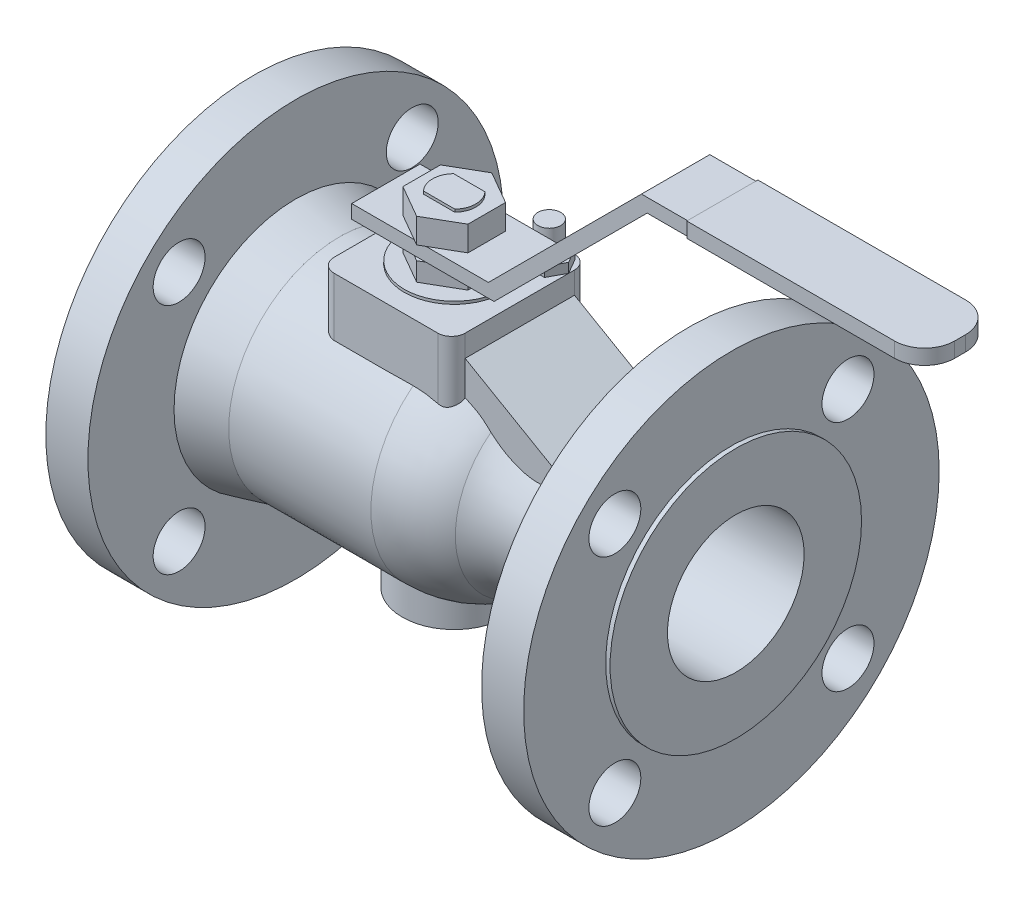
SolidWorks part; units mm, degrees
ref_plane "Alzado" through (0, 0, 0) normal (0, 0, 1) x (1, 0, 0)
ref_plane "Planta" through (0, 0, 0) normal (0, 1, 0) x (1, 0, 0)
ref_plane "Vista lateral" through (0, 0, 0) normal (1, 0, 0) x (0, 0, -1)
sketch "Sketch1" plane through (0, 0, 0) normal (0, 1, 0) x (1, 0, 0)
  line L0 (0, 0) -> (-58, 0)
  line L2 (0, 0) -> (86, 0)
  line L82 (86, -25) -> (86, 0)
  line L83 (103, -25) -> (86, -25)
  line L84 (103, -46) -> (103, -25)
  line L85 (101.4, -46) -> (103, -46)
  line L86 (101.4, -76) -> (101.4, -46)
  line L87 (86, -76) -> (101.4, -76)
  line L88 (86, -46.5259) -> (86, -76)
  line L89 (60.6645, -29.1709) -> (77.9489, -35.1943)
  line L90 (-42, -40.5) -> (10, -40.5)
  line L91 (-58, -44.5) -> (-42, -40.5)
  line L92 (-58, -76) -> (-58, -44.5)
  line L93 (-73.4, -76) -> (-58, -76)
  line L94 (-73.4, -46) -> (-73.4, -76)
  line L95 (-75, -46) -> (-73.4, -46)
  line L96 (-75, -25) -> (-75, -46)
  line L97 (-58, -25) -> (-75, -25)
  line L98 (-58, 0) -> (-58, -25)
  arc A10 (86, -46.5259) -> (77.9489, -35.1943) centre (74, -46.5259) ccw
  arc A11 (60.6645, -29.1709) -> (33.4338, -33.0319) centre (50.7922, -57.5) ccw
  spline S5 degree 3 poles (10, -40.5) (10.5262, -40.5101) (11.0548, -40.5089) (12.1058, -40.4845) (12.6294, -40.4614) (14.1952, -40.3616) (15.2323, -40.2548) (18.3249, -39.8235) (20.3622, -39.3913) (23.3756, -38.4904) (24.3775, -38.1449) (26.3277, -37.3691) (27.2787, -36.9384) (30.0543, -35.5088) (31.8008, -34.3712) (33.4338, -33.0319) knots 0 0 0 0 0.0625 0.0625 0.125 0.125 0.25 0.25 0.5 0.5 0.625 0.625 0.75 0.75 1 1 1 1
revolve "Revolve1" add sketch "Sketch1" angle 360 about L0
sketch "Sketch2" plane through (0, 0, 0) normal (1, 0, 0) x (0, 0, -1)
  circle A4 centre (-42.6385, 42.6385) radius 9.5
  circle A5 centre (-42.6385, -42.6385) radius 9.5
  circle A6 centre (42.6385, 42.6385) radius 9.5
  circle A7 centre (42.6385, -42.6385) radius 9.5
extrude "Cut-Extrude1" cut sketch "Sketch2" against normal through all both and the other way through all
sketch "Sketch3" plane through (0, 0, 0) normal (0, 1, 0) x (1, 0, 0)
  circle A2 centre (0, 0) radius 19
extrude "Boss-Extrude1" add sketch "Sketch3" against normal blind 49.5 separate body
sketch "Sketch4" plane through (0, 0, 0) normal (0, 1, 0) x (1, 0, 0)
  line L27 (19, 25) -> (-19, 25)
  line L28 (-24, 20) -> (-24, -20)
  line L29 (-19, -25) -> (19, -25)
  line L30 (24, -20) -> (24, 20)
  arc A8 (24, 20) -> (19, 25) centre (19, 20) ccw
  arc A9 (-19, 25) -> (-24, 20) centre (-19, 20) ccw
  arc A10 (-24, -20) -> (-19, -25) centre (-19, -20) ccw
  arc A11 (19, -25) -> (24, -20) centre (19, -20) ccw
extrude "Boss-Extrude2" add sketch "Sketch4" along normal blind 53 separate body
sketch "Sketch5" plane through (0, 53, 0) normal (0, 1, 0) x (1, 0, 0)
  line L22 (20.882, 12.1277) -> (14.4734, 12.1277)
  line L23 (14.4734, 12.1277) -> (11.2691, 17.6777)
  line L24 (11.2691, 17.6777) -> (14.4734, 23.2277)
  line L25 (14.4734, 23.2277) -> (20.882, 23.2277)
  line L26 (20.882, 23.2277) -> (24, 17.8271)
  line L32 (24, 17.8271) -> (20.882, 12.1277)
extrude "Boss-Extrude3" add sketch "Sketch5" along normal blind 3.5 separate body
sketch "Sketch6" plane through (0, 56.5, 0) normal (0, 1, 0) x (1, 0, 0)
  circle A0 centre (17.2247, 17.5586) radius 4.1811
extrude "Boss-Extrude4" add sketch "Sketch6" along normal blind 10.5 separate body
sketch "Sketch7" plane through (0, 0, 0) normal (0, 0, 1) x (1, 0, 0)
  line L0 (0, 0) -> (131.7104, 0) construction
  line L4 (63.1369, 22.4043) -> (24, 45)
  line L5 (24, 45) -> (24.0001, 32.3146)
  spline S6 degree 3 poles (33.4338, 26.2889) (34.3576, 25.4654) (35.3154, 24.6958) (37.3021, 23.2697) (38.331, 22.6131) (40.4691, 21.4275) (41.5792, 20.8979) (43.893, 19.9956) (45.0677, 19.6346) (47.4558, 19.1103) (48.6693, 18.947) (50.522, 18.8671) (51.1466, 18.8683) (52.3887, 18.9271) (53.0096, 18.9848) (54.8557, 19.2385) (56.0549, 19.513) (58.3989, 20.2432) (59.5438, 20.6989) (60.6645, 21.2354) knots 0 0 0 0 0.125 0.125 0.25 0.25 0.375 0.375 0.5 0.5 0.625 0.625 0.6875 0.6875 0.75 0.75 0.875 0.875 1 1 1 1
  spline S7 degree 3 poles (60.6645, 21.2354) (61.4867, 21.629) (62.311, 22.0185) (63.1369, 22.4043) knots 0 0 0 0 1 1 1 1
  spline S8 degree 3 poles (24.0001, 32.3146) (24.8648, 31.9406) (25.7146, 31.5304) (27.3704, 30.6494) (28.1774, 30.1777) (29.7503, 29.1727) (30.516, 28.6394) (32.0063, 27.511) (32.7311, 26.9166) (33.4338, 26.2889) knots 0 0 0 0 0.25 0.25 0.5 0.5 0.75 0.75 1 1 1 1
extrude "Boss-Extrude5" add sketch "Sketch7" along normal blind 20 and the other way blind 20 separate body
sketch "Sketch8" plane through (0, 53, 0) normal (0, 1, 0) x (1, 0, 0)
  line L0 (0, 0) -> (29.0528, -1.511) construction
  circle A1 centre (0, 0) radius 18.25
extrude "Boss-Extrude6" add sketch "Sketch8" along normal blind 1 separate body
sketch "Sketch9" plane through (0, 54, 0) normal (0, 1, 0) x (1, 0, 0)
  line L0 (0, 0) -> (32.4906, 0) construction
  line L13 (-11.9, 6.8705) -> (-11.9, -6.8705)
  line L14 (-11.9, -6.8705) -> (0, -13.7409)
  line L15 (0, -13.7409) -> (11.9, -6.8705)
  line L16 (11.9, -6.8705) -> (11.9, 6.8705)
  line L17 (11.9, 6.8705) -> (0, 13.7409)
  line L18 (0, 13.7409) -> (-11.9, 6.8705)
extrude "Boss-Extrude7" add sketch "Sketch9" along normal blind 20.9 separate body
sketch "Sketch10" plane through (0, 74.9, 0) normal (0, 1, 0) x (1, 0, 0)
  line L4 (5.725, 5.5) -> (-5.725, 5.5)
  line L5 (-5.725, -5.5) -> (5.725, -5.5)
  arc A4 (5.725, -5.5) -> (5.725, 5.5) centre (0, 0) ccw
  arc A5 (-5.725, 5.5) -> (-5.725, -5.5) centre (0, 0) ccw
extrude "Boss-Extrude8" add sketch "Sketch10" along normal blind 1 separate body
sketch "Sketch11" plane through (0, 0, 0) normal (0, 0, 1) x (1, 0, 0)
  line L8 (98.0711, 122.05) -> (98.0711, 116.55)
  line L9 (98.0711, 116.55) -> (185.0711, 116.55)
  line L10 (185.0711, 116.55) -> (185.0711, 122.05)
  line L11 (185.0711, 122.05) -> (98.0711, 122.05)
extrude "Boss-Extrude9" add sketch "Sketch11" along normal blind 13 and the other way blind 13 separate body
sketch "Sketch12" plane through (0, 0, 0) normal (0, 0, 1) x (1, 0, 0)
  line L24 (2.1494, 60.8) -> (27.0711, 60.8)
  line L25 (27.0711, 60.8) -> (83.0711, 116.8)
  line L26 (83.0711, 116.8) -> (98.0711, 116.8)
  line L27 (98.0711, 116.8) -> (98.0711, 121.8)
  line L28 (98.0711, 121.8) -> (81, 121.8)
  line L29 (81, 121.8) -> (25, 65.8)
  line L30 (25, 65.8) -> (2.1494, 65.8)
  line L31 (2.1494, 65.8) -> (-2.1494, 65.8)
  line L32 (-2.1494, 65.8) -> (-25, 65.8)
  line L33 (-25, 65.8) -> (-25, 60.8)
  line L34 (-25, 60.8) -> (-2.1494, 60.8)
  line L35 (-2.1494, 60.8) -> (2.1494, 60.8)
extrude "Boss-Extrude10" add sketch "Sketch12" along normal blind 12.5 and the other way blind 12.5 separate body
sketch "Sketch13" plane through (-25, 0, 0) normal (-1, 0, 0) x (0, 0, 1)
  line L0 (-12.5, 60.8) -> (12.5, 60.8) construction
  line L1 (12.5, 65.8) -> (30.754, 65.8)
  line L3 (12.5, 60.8) -> (30.754, 60.8)
  line L4 (30.754, 65.8) -> (30.754, 60.8)
  line L5 (-12.5, 65.8) -> (-31.0131, 65.8)
  line L6 (-12.5, 65.8) -> (-12.5, 60.8)
  line L7 (-12.5, 60.8) -> (-31.0131, 60.8)
  line L8 (-31.0131, 65.8) -> (-31.0131, 60.8)
  line L9 (-12.5, 65.8) -> (-12.5, 60.8) construction
  line M2 (12.5, 60.8) -> (12.5, 65.8)
  line M4 (-12.5, 65.8) -> (-12.5, 60.8)
extrude "Cut-Extrude2" cut sketch "Sketch13" against normal blind 33.5 contours L5 L8 L7 M4 | L4 L1 L3 M2 region at (-25, 63.3, 21.627) region at (-25, 63.3, -21.7565)
other "PuntoR1"
sketch "Sketch14" plane through (0, 0, 0) normal (0, 0, 1) x (1, 0, 0)
  line L0 (-75, 0) -> (0, 0)
  line L1 (-75, 46) -> (-75, -46) construction
  line L2 (0, 0) -> (103, 0)
  line L3 (103, -46) -> (103, 46) construction
ref_axis "Vertical" through (0, 131.9525, 0) along (0, -1, 0)
other "CPoint1" parameters "Diameter"=50.8, "StubLength"=0
ref_axis "Axis2" through (-85, 0, 0) along (1, 0, 0)
other "CPoint2" parameters "Diameter"=50.8, "StubLength"=0
ref_axis "Axis3" through (113, 0, 0) along (-1, 0, 0)
fillet "Fillet1" radius 11 2 edges at (185.0711, 119.3, -13) (185.0711, 119.3, 13)
sketch "Sketch15" plane through (-75, 0, 0) normal (-1, 0, 0) x (0, 0, 1)
  circle A0 centre (0, 0) radius 25 construction
  circle A1 centre (0, 0) radius 25
extrude "Cut-Extrude3" cut sketch "Sketch15" against normal through all
